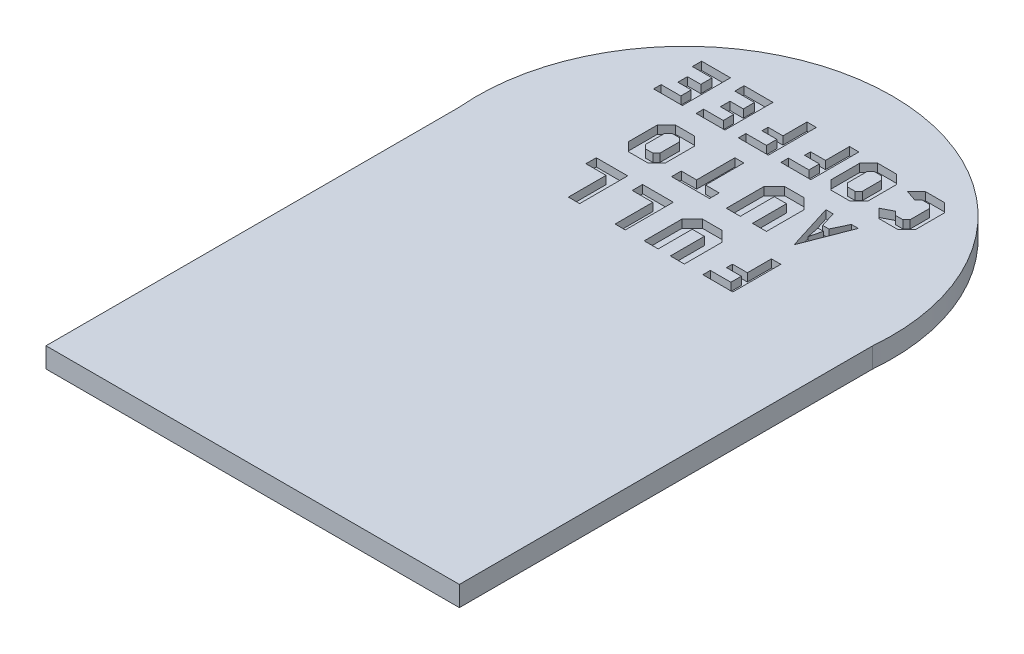
SolidWorks part; units mm, degrees
ref_plane "Front Plane" through (0, 0, 0) normal (0, 0, 1) x (1, 0, 0)
ref_plane "Top Plane" through (0, 0, 0) normal (0, 1, 0) x (1, 0, 0)
ref_plane "Right Plane" through (0, 0, 0) normal (1, 0, 0) x (0, 0, -1)
sketch "Sketch1" plane through (0, 0, 0) normal (0, 1, 0) x (1, 0, 0)
  line L0 (0, 0) -> (0, 44.2645)
  line L1 (-97.7175, 44.2645) -> (-97.7175, -151.1705)
  line L2 (-97.7175, -151.1705) -> (97.7175, -151.1705)
  line L3 (97.7175, -151.1705) -> (97.7175, 44.2645)
  line L4 (-97.7175, 44.2645) -> (97.7175, 44.2645)
  arc A0 (97.7175, 44.2645) -> (-97.7175, 44.2645) centre (0, 53.0581) ccw
  point P7 (0, 0)
  dimension "D3" = 98.1124
  dimension "D1" = 195.435
  dimension "D2" = 195.435
extrude "Boss-Extrude1" add sketch "Sketch1" along normal blind 9.525 contours L4 L1 L2 L3 | L4 A0 region at (0, 0, 53.453) region at (0, 0, -89.9888)
sketch "Sketch6" plane through (0, 9.525, 0) normal (0, 1, 0) x (1, 0, 0)
  line L152 (33.0927, 98.124) -> (37.3382, 102.3695)
  line L153 (37.3382, 102.3695) -> (37.3382, 115.9362)
  line L154 (37.3382, 115.9362) -> (33.0927, 120.1817)
  line L155 (33.0927, 120.1817) -> (24.1346, 120.1817)
  line L156 (24.1346, 120.1817) -> (19.8891, 115.9362)
  line L157 (19.8891, 115.9362) -> (19.8891, 102.3695)
  line L158 (19.8891, 102.3695) -> (24.1346, 98.124)
  line L159 (24.1346, 98.124) -> (33.0927, 98.124)
  line L160 (32.0091, 105.0572) -> (32.0091, 114.2233)
  line L161 (32.0091, 114.2233) -> (30.2961, 115.9362)
  line L162 (30.2961, 115.9362) -> (26.764, 115.9362)
  line L163 (26.764, 115.9362) -> (25.051, 114.2233)
  line L164 (25.051, 114.2233) -> (25.051, 105.0572)
  line L165 (25.051, 105.0572) -> (26.764, 103.3443)
  line L166 (26.764, 103.3443) -> (30.2961, 103.3443)
  line L167 (30.2961, 103.3443) -> (32.0091, 105.0572)
  line L168 (15.0964, 120.3415) -> (15.0964, 97.632)
  line L169 (15.0964, 97.632) -> (0.9387, 97.632)
  line L170 (0.9387, 97.632) -> (0.9387, 101.1697)
  line L171 (0.9387, 101.1697) -> (10.6454, 101.1697)
  line L172 (10.6454, 101.1697) -> (10.6454, 106.1182)
  line L173 (10.6454, 106.1182) -> (3.6033, 106.1182)
  line L174 (3.6033, 106.1182) -> (3.6033, 108.9868)
  line L175 (3.6033, 108.9868) -> (10.6454, 108.9868)
  line L176 (10.6454, 108.9868) -> (10.6454, 120.3415)
  line L177 (10.6454, 120.3415) -> (15.0964, 120.3415)
  line L178 (-5.0014, 120.3415) -> (-5.0014, 97.632)
  line L179 (-5.0014, 97.632) -> (-19.1591, 97.632)
  line L180 (-19.1591, 97.632) -> (-19.1591, 101.1697)
  line L181 (-19.1591, 101.1697) -> (-9.4525, 101.1697)
  line L182 (-9.4525, 101.1697) -> (-9.4525, 106.1182)
  line L183 (-9.4525, 106.1182) -> (-16.4945, 106.1182)
  line L184 (-16.4945, 106.1182) -> (-16.4945, 108.9868)
  line L185 (-16.4945, 108.9868) -> (-9.4525, 108.9868)
  line L186 (-9.4525, 108.9868) -> (-9.4525, 120.3415)
  line L187 (-9.4525, 120.3415) -> (-5.0014, 120.3415)
  line L188 (-25.5301, 97.632) -> (-25.5301, 120.3415)
  line L189 (-25.5301, 120.3415) -> (-39.1542, 120.3415)
  line L190 (-39.1542, 120.3415) -> (-39.1542, 115.9362)
  line L191 (-39.1542, 115.9362) -> (-29.8527, 115.9362)
  line L192 (-29.8527, 115.9362) -> (-29.8527, 110.6477)
  line L193 (-29.8527, 110.6477) -> (-36.1645, 110.6477)
  line L194 (-36.1645, 110.6477) -> (-36.1645, 106.1182)
  line L195 (-36.1645, 106.1182) -> (-29.8527, 106.1182)
  line L196 (-29.8527, 106.1182) -> (-29.8527, 101.1697)
  line L197 (-29.8527, 101.1697) -> (-39.1542, 101.1697)
  line L198 (-39.1542, 101.1697) -> (-39.1542, 97.632)
  line L199 (-39.1542, 97.632) -> (-25.5301, 97.632)
  line L200 (-45.63, 97.632) -> (-45.63, 120.3415)
  line L201 (-45.63, 120.3415) -> (-59.2541, 120.3415)
  line L202 (-59.2541, 120.3415) -> (-59.2541, 115.9362)
  line L203 (-59.2541, 115.9362) -> (-49.9526, 115.9362)
  line L204 (-49.9526, 115.9362) -> (-49.9526, 110.6477)
  line L205 (-49.9526, 110.6477) -> (-56.2643, 110.6477)
  line L206 (-56.2643, 110.6477) -> (-56.2643, 106.1182)
  line L207 (-56.2643, 106.1182) -> (-49.9526, 106.1182)
  line L208 (-49.9526, 106.1182) -> (-49.9526, 101.1697)
  line L209 (-49.9526, 101.1697) -> (-59.2541, 101.1697)
  line L210 (-59.2541, 101.1697) -> (-59.2541, 97.632)
  line L211 (-59.2541, 97.632) -> (-45.63, 97.632)
  line L212 (56.0141, 97.7918) -> (60.2597, 102.0374)
  line L213 (60.2597, 102.0374) -> (60.2597, 115.604)
  line L214 (60.2597, 115.604) -> (56.0141, 119.8495)
  line L215 (56.0141, 119.8495) -> (47.0561, 119.8495)
  line L216 (47.0561, 119.8495) -> (42.8106, 115.604)
  line L217 (42.8106, 102.0374) -> (47.0561, 97.7918)
  line L218 (47.0561, 97.7918) -> (56.0141, 97.7918)
  line L219 (54.9305, 104.725) -> (54.9305, 113.8911)
  line L220 (54.9305, 113.8911) -> (53.2176, 115.604)
  line L221 (53.2176, 115.604) -> (49.6855, 115.604)
  line L222 (49.6855, 115.604) -> (47.9725, 113.8911)
  line L223 (47.9725, 104.725) -> (49.6855, 103.0121)
  line L224 (49.6855, 103.0121) -> (53.2176, 103.0121)
  line L225 (53.2176, 103.0121) -> (54.9305, 104.725)
  line L226 (47.9725, 104.725) -> (42.8106, 102.0374)
  line L227 (47.9725, 113.8911) -> (42.8106, 115.604)
  line L228 (46.2567, 88.9065) -> (37.7701, 67.0259)
  line L229 (37.7701, 67.0259) -> (30.9232, 88.9065)
  line L230 (30.9232, 88.9065) -> (34.3467, 88.9065)
  line L231 (34.3467, 88.9065) -> (36.5954, 81.7202)
  line L232 (36.5954, 81.7202) -> (39.5563, 81.7202)
  line L233 (39.5563, 81.7202) -> (42.9798, 88.9065)
  line L234 (42.9798, 88.9065) -> (46.2567, 88.9065)
  line L235 (39.1736, 79.4766) -> (37.7701, 73.5961)
  line L236 (37.7701, 73.5961) -> (36.5954, 79.4766)
  line L237 (36.5954, 79.4766) -> (39.1736, 79.4766)
  line L238 (25.7801, 65.95) -> (25.7801, 83.7621)
  line L239 (25.7801, 83.7621) -> (20.8829, 88.6594)
  line L240 (20.8829, 88.6594) -> (11.696, 88.6594)
  line L241 (11.696, 88.6594) -> (6.7987, 83.7621)
  line L242 (6.7987, 83.7621) -> (6.7987, 65.95)
  line L243 (6.7987, 65.95) -> (13.4089, 65.95)
  line L244 (13.4089, 65.95) -> (13.4089, 82.0492)
  line L245 (13.4089, 82.0492) -> (19.1699, 82.0492)
  line L246 (19.1699, 82.0492) -> (19.1699, 65.95)
  line L247 (19.1699, 65.95) -> (25.7801, 65.95)
  line L248 (-1.1551, 65.95) -> (-19.0989, 65.95)
  line L249 (-19.0989, 65.95) -> (-19.0989, 70.5469)
  line L250 (-19.0989, 70.5469) -> (-11.8419, 70.5469)
  line L251 (-11.8419, 70.5469) -> (-11.8419, 88.6594)
  line L252 (-11.8419, 88.6594) -> (-7.5986, 88.6594)
  line L253 (-7.5986, 88.6594) -> (-7.5986, 70.5469)
  line L254 (-7.5986, 70.5469) -> (-1.1551, 70.5469)
  line L255 (-1.1551, 70.5469) -> (-1.1551, 65.95)
  line L256 (-30.3865, 65.95) -> (-26.141, 70.1955)
  line L257 (-26.141, 70.1955) -> (-26.141, 83.7621)
  line L258 (-26.141, 83.7621) -> (-30.3865, 88.0077)
  line L259 (-30.3865, 88.0077) -> (-39.3445, 88.0077)
  line L260 (-39.3445, 88.0077) -> (-43.5901, 83.7621)
  line L261 (-43.5901, 83.7621) -> (-43.5901, 70.1955)
  line L262 (-43.5901, 70.1955) -> (-39.3445, 65.95)
  line L263 (-39.3445, 65.95) -> (-30.3865, 65.95)
  line L264 (-31.4701, 72.8832) -> (-31.4701, 82.0492)
  line L265 (-31.4701, 82.0492) -> (-33.1831, 83.7621)
  line L266 (-33.1831, 83.7621) -> (-36.7152, 83.7621)
  line L267 (-36.7152, 83.7621) -> (-38.4282, 82.0492)
  line L268 (-38.4282, 82.0492) -> (-38.4282, 72.8832)
  line L269 (-38.4282, 72.8832) -> (-36.7152, 71.1702)
  line L270 (-36.7152, 71.1702) -> (-33.1831, 71.1702)
  line L271 (-33.1831, 71.1702) -> (-31.4701, 72.8832)
  line L272 (42.6295, 55.8956) -> (42.6295, 33.1861)
  line L273 (42.6295, 33.1861) -> (28.4718, 33.1861)
  line L274 (28.4718, 33.1861) -> (28.4718, 36.7238)
  line L275 (28.4718, 36.7238) -> (38.1785, 36.7238)
  line L276 (38.1785, 36.7238) -> (38.1785, 41.6723)
  line L277 (38.1785, 41.6723) -> (31.1364, 41.6723)
  line L278 (31.1364, 41.6723) -> (31.1364, 44.5409)
  line L279 (31.1364, 44.5409) -> (38.1785, 44.5409)
  line L280 (38.1785, 44.5409) -> (38.1785, 55.8956)
  line L281 (38.1785, 55.8956) -> (42.6295, 55.8956)
  line L282 (19.7168, 33.1861) -> (19.7168, 50.9983)
  line L283 (19.7168, 50.9983) -> (14.8195, 55.8956)
  line L284 (14.8195, 55.8956) -> (5.6326, 55.8956)
  line L285 (5.6326, 55.8956) -> (0.7353, 50.9983)
  line L286 (0.7353, 50.9983) -> (0.7353, 33.1861)
  line L287 (0.7353, 33.1861) -> (7.3456, 33.1861)
  line L288 (7.3456, 33.1861) -> (7.3456, 49.2854)
  line L289 (7.3456, 49.2854) -> (13.1066, 49.2854)
  line L290 (13.1066, 49.2854) -> (13.1066, 33.1861)
  line L291 (13.1066, 33.1861) -> (19.7168, 33.1861)
  line L292 (-8.1994, 33.1861) -> (-8.1994, 55.8956)
  line L293 (-8.1994, 55.8956) -> (-22.7261, 55.8956)
  line L294 (-22.7261, 55.8956) -> (-22.7261, 50.9983)
  line L295 (-22.7261, 50.9983) -> (-13.0194, 50.9983)
  line L296 (-13.0194, 50.9983) -> (-13.0194, 33.1861)
  line L297 (-13.0194, 33.1861) -> (-8.1994, 33.1861)
  line L298 (-29.7682, 33.1861) -> (-29.7682, 55.8956)
  line L299 (-29.7682, 55.8956) -> (-44.6136, 55.8956)
  line L300 (-44.6136, 55.8956) -> (-44.6136, 50.9983)
  line L301 (-44.6136, 50.9983) -> (-35.0973, 50.9983)
  line L302 (-35.0973, 50.9983) -> (-35.0973, 33.1861)
  line L303 (-35.0973, 33.1861) -> (-29.7682, 33.1861)
extrude "Cut-Extrude2" cut sketch "Sketch6" against normal blind 3.81
